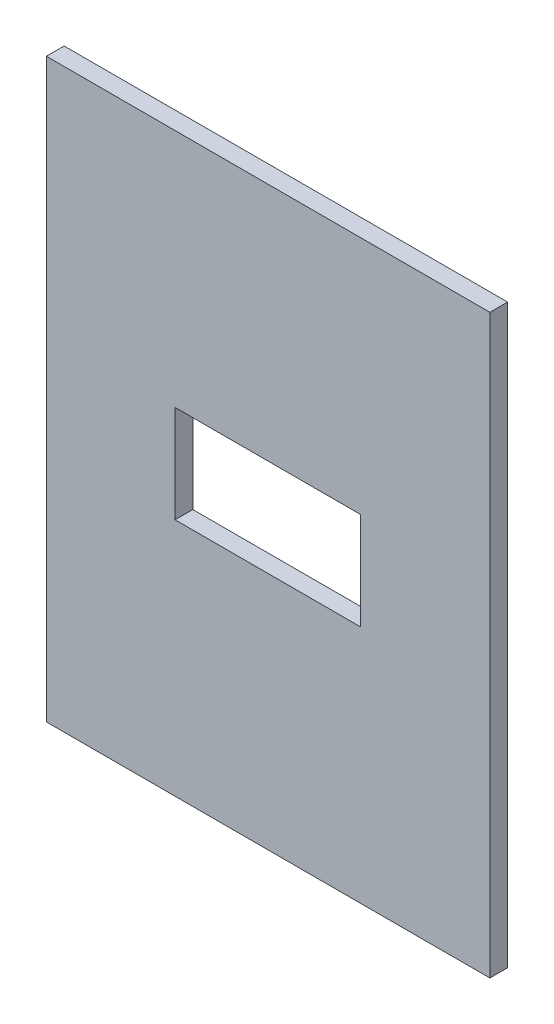
SolidWorks part; units mm, degrees
ref_plane "Ön Düzlem" through (0, 0, 0) normal (0, 0, 1) x (1, 0, 0)
ref_plane "Üst Düzlem" through (0, 0, 0) normal (0, 1, 0) x (1, 0, 0)
ref_plane "Sağ Düzlem" through (0, 0, 0) normal (1, 0, 0) x (0, 0, -1)
sketch "Sketch1" plane through (0, 0, 0) normal (0, 0, 1) x (1, 0, 0)
  line L0 (0, 0) -> (100, 0)
  line L1 (0, 0) -> (0, 130)
  line L2 (100, 0) -> (100, 130)
  line L3 (0, 130) -> (100, 130)
  dimension "D1" = 130
  dimension "D2" = 100
extrude "Boss-Extrude1" add sketch "Sketch1" along normal blind 4
sketch "Sketch3" plane through (0, 0, 4) normal (0, 0, 1) x (1, 0, 0)
  line L0 (29.0135, 75.9303) -> (29.0135, 53.987)
  line L1 (29.0135, 75.9303) -> (70.8554, 75.9303)
  line L2 (29.0135, 53.987) -> (70.8554, 53.987)
  line L3 (70.8554, 75.9303) -> (70.8554, 53.987)
extrude "Cut-Extrude2" cut sketch "Sketch3" against normal blind 10
